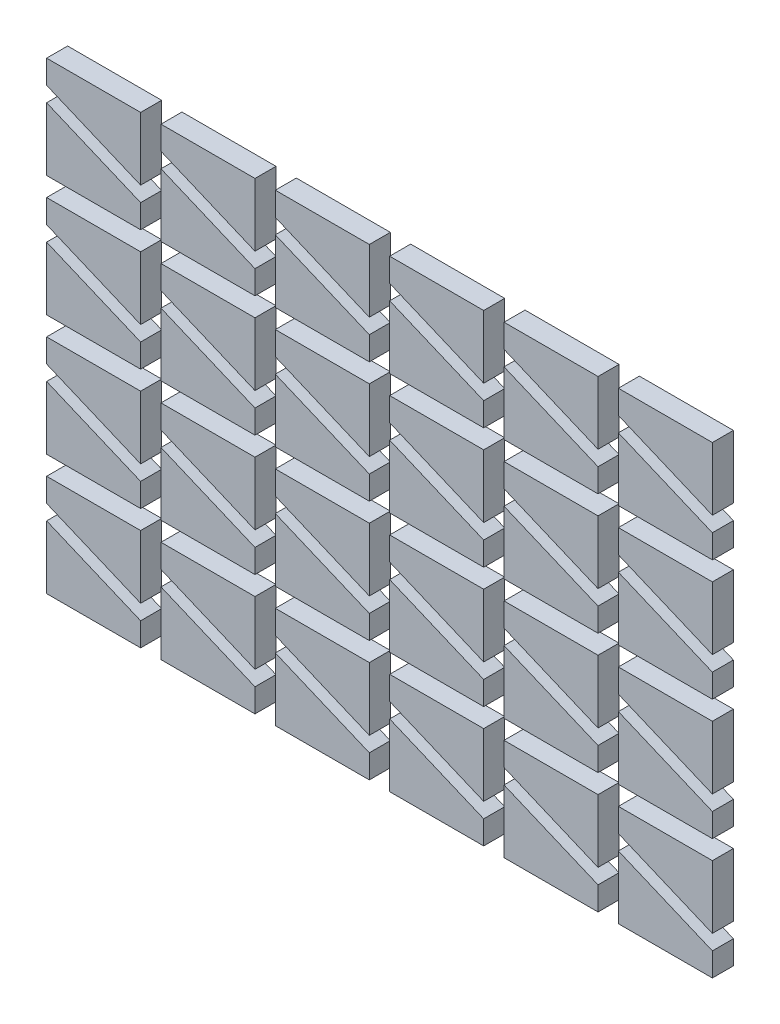
SolidWorks part; units mm, degrees
ref_plane "Front Plane" through (0, 0, 0) normal (0, 0, 1) x (1, 0, 0)
ref_plane "Top Plane" through (0, 0, 0) normal (0, 1, 0) x (1, 0, 0)
ref_plane "Right Plane" through (0, 0, 0) normal (1, 0, 0) x (0, 0, -1)
sketch "Sketch1" plane through (0, 0, 0) normal (0, 0, 1) x (1, 0, 0)
  line L0 (-4.699, -5.08) -> (4.699, -5.08)
  line L1 (4.699, -5.08) -> (4.699, -2.7305)
  line L2 (4.699, -2.7305) -> (-4.699, 1.2192)
  line L3 (-4.699, 1.2192) -> (-4.699, -5.08)
  point P3 (0, 0)
  point P6 (0, 0)
  point P8 (0, 0)
  point P9 (1.1625, -3.7011)
  point P11 (-4.8703, 1.1668)
  point P13 (0, -5.08)
  dimension "D1" = 6.2992
  dimension "D2" = 2.3495
  dimension "D3" = 9.398
  dimension "D4" = 5.08
extrude "Boss-Extrude1" add sketch "Sketch1" along normal mid plane 2.1
ref_axis "Axis1" through (0, 0, 1.155) along (0, 0, -1)
pattern_circular "CirPattern1" count 2 over 360 about axis through (0, 0, 1.155) along (0, 0, -1) of "Boss-Extrude1"
pattern_linear "LPattern1" count 4 spacing 12.065 along (0, 1, 0) count 6 spacing 11.43 along (1, 0, 0) of bodies 102 101
